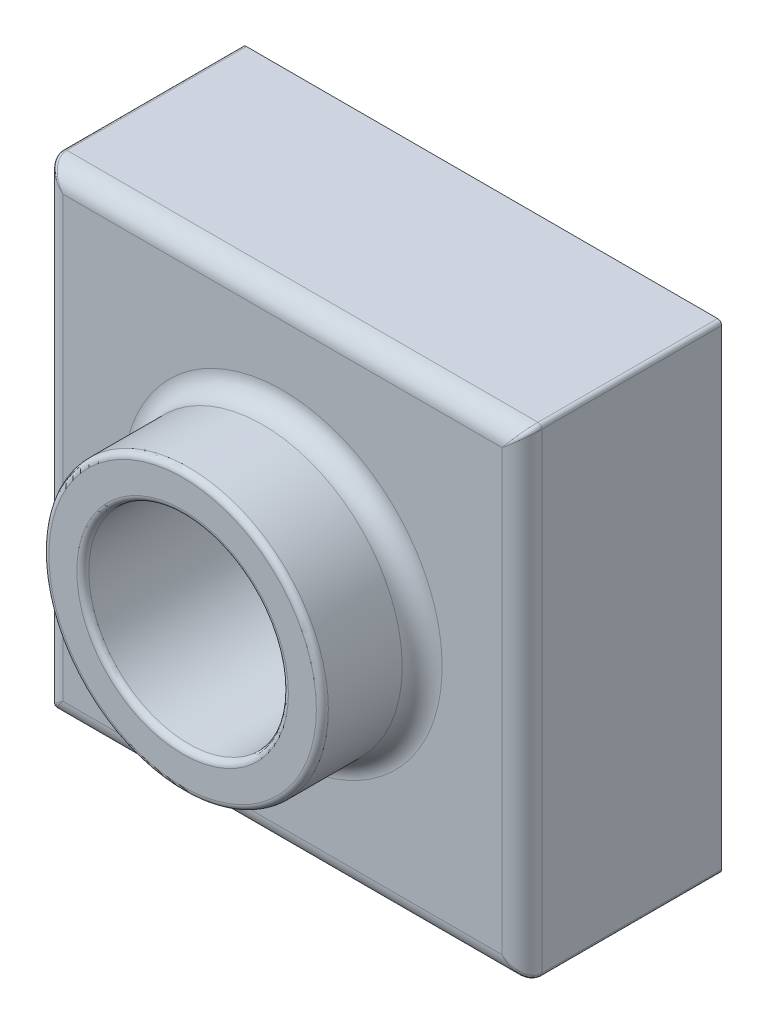
SolidWorks part; units mm, degrees
material "Chrome Stainless Steel"
ref_plane "Front Plane" through (0, 0, 0) normal (0, 0, 1) x (1, 0, 0)
ref_plane "Top Plane" through (0, 0, 0) normal (0, 1, 0) x (1, 0, 0)
ref_plane "Right Plane" through (0, 0, 0) normal (1, 0, 0) x (0, 0, -1)
sketch "Sketch1" plane through (0, 0, 0) normal (0, 0, 1) x (1, 0, 0)
  line L0 (0, 0) -> (0, 120)
  line L1 (0, 120) -> (120, 120)
  line L2 (120, 120) -> (120, 0)
  line L3 (120, 0) -> (0, 0)
  dimension "D1" = 120
  dimension "D2" = 120
extrude "Boss-Extrude1" add sketch "Sketch1" along normal blind 50
sketch "Sketch4" plane through (0, 0, 50) normal (0, 0, 1) x (1, 0, 0)
  line L0 (120, 120) -> (0, 120) construction
  line L1 (120, 0) -> (120, 120) construction
  circle A0 centre (60, 60) radius 35
  dimension "D1" = 70
  dimension "D2" = 60
  dimension "D3" = 60
extrude "Boss-Extrude2" add sketch "Sketch4" along normal blind 25
sketch "Sketch6" plane through (0, 0, 75) normal (0, 0, 1) x (1, 0, 0)
  circle A0 centre (60, 60) radius 25
  dimension "D1" = 50
extrude "Cut-Extrude1" cut sketch "Sketch6" against normal through all
fillet "Fillet1" radius 1 4 edges at (120, 120, 25) (0, 120, 25) (0, 0, 25) (120, 0, 25)
fillet "Fillet2" radius 1.5 2 edges at (95, 60, 75) (85, 60, 75)
shell "Shell1" thickness 2 removed face at (85, 60, 0)
fillet "Fillet3" radius 5 9 edges at (0.2929, 0.2929, 50) (0, 60, 50) (0.2929, 119.7071, 50) (60, 120, 50) (119.7071, 119.7071, 50) (120, 60, 50) (119.7071, 0.2929, 50) (60, 0, 50) (95, 60, 50)
